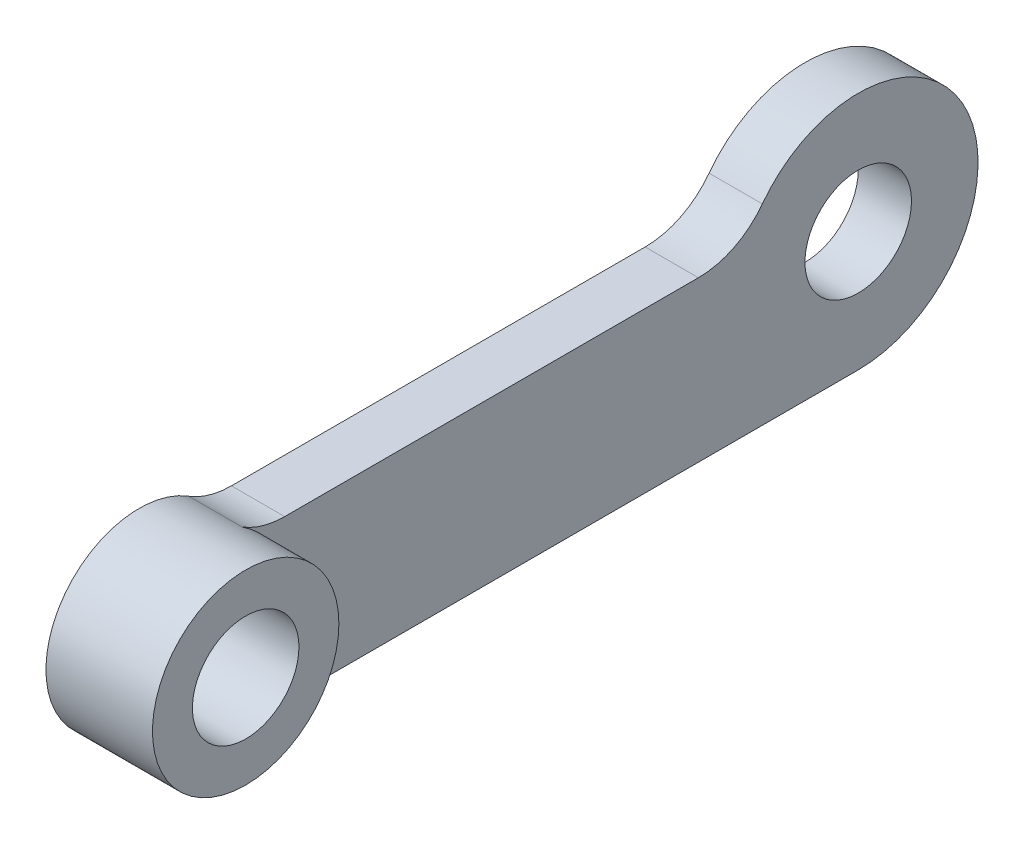
SolidWorks part; units mm, degrees
ref_plane "前视基准面" through (0, 0, 0) normal (0, 0, 1) x (1, 0, 0)
ref_plane "上视基准面" through (0, 0, 0) normal (0, 1, 0) x (1, 0, 0)
ref_plane "右视基准面" through (0, 0, 0) normal (1, 0, 0) x (0, 0, -1)
other "Configuration Table"
sketch "草图1" plane through (0, 0, 0) normal (1, 0, 0) x (0, 0, -1)
  line L1 (0, 0) -> (25, 0)
  line L2 (0, 0) -> (0, -6)
  line L3 (0, -6) -> (25, -6)
  line L4 (25, 0) -> (25, -6)
  circle A0 centre (0, -2.5) radius 3.5
  circle A1 centre (25, -1.5) radius 4.5
  circle A2 centre (0, -2.5) radius 2
  circle A3 centre (25, -1.5) radius 2
  dimension "D1" = 7
  dimension "D2" = 9
  dimension "D4" = 4
  dimension "D3" = 6
  dimension "D5" = 25
extrude "凸台-拉伸1" add sketch "草图1" along normal blind 2 contours A0 | L1 L4 L3 L2 | A1
extrude "凸台-拉伸3" add sketch "草图1<5>" along normal blind 2 from surface contours A0 starting at face at (2, -1.5198, -12.3843)
sketch "草图1<5>" plane through (0, 0, 0) normal (1, 0, 0) x (0, 0, -1) same geometry as "草图1"
extrude "切除-拉伸2" cut sketch "草图1<4>" along normal through all both and the other way through all contours L2 A2 | L2 A2 | L4 A3 L1 | L1 A3 L4 region at (0, -2.5, -0.8488) region at (0, -2.5, 0.8488) region at (0, -1.3854, -25.7577) region at (0, -1.6324, -24.1245)
sketch "草图1<4>" plane through (0, 0, 0) normal (1, 0, 0) x (0, 0, -1) same geometry as "草图1"
fillet "圆角1" radius 3 2 edges at (1, 0, -20.7574) (1, 0, -2.4495)
